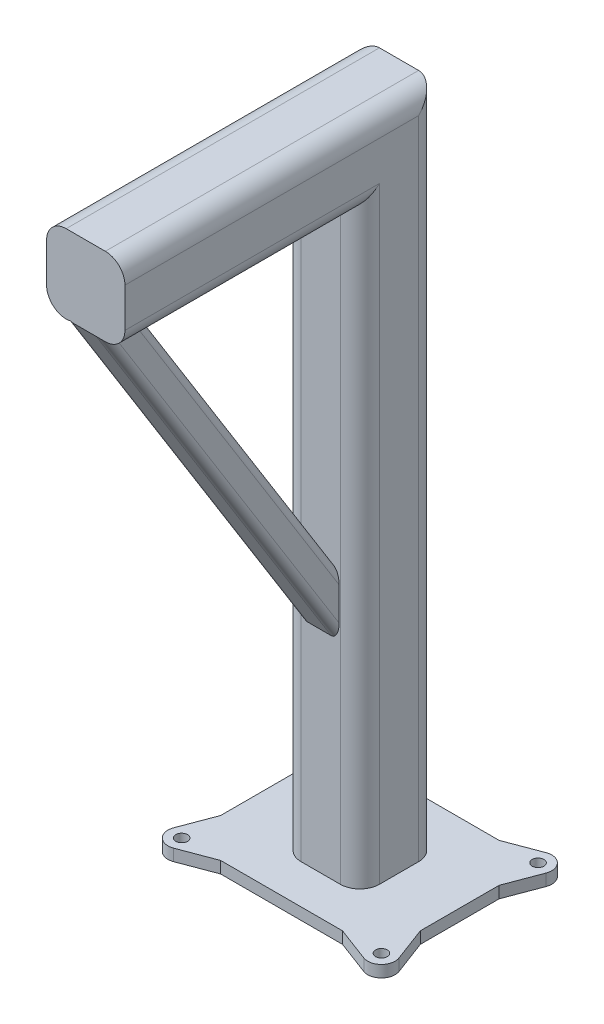
SolidWorks part; units mm, degrees
ref_plane "前视基准面" through (0, 0, 0) normal (0, 0, 1) x (1, 0, 0)
ref_plane "上视基准面" through (0, 0, 0) normal (0, 1, 0) x (1, 0, 0)
ref_plane "右视基准面" through (0, 0, 0) normal (1, 0, 0) x (0, 0, -1)
other "Configuration Table"
sketch "Sketch1" plane through (0, 0, 0) normal (0, 1, 0) x (1, 0, 0)
  line L0 (-24.2665, 23.2754) -> (-15.5689, 20)
  line L10 (24.2665, 23.2754) -> (15.5689, 20)
  line L11 (24.2665, -23.2754) -> (15.5689, -20)
  line L12 (-24.2665, -23.2754) -> (-15.5689, -20)
  line L13 (-28.7754, 18.7665) -> (-25.5, 10.0689)
  line L14 (28.7754, 18.7665) -> (25.5, 10.0689)
  line L15 (28.7754, -18.7665) -> (25.5, -10.0689)
  line L16 (-28.7754, -18.7665) -> (-25.5, -10.0689)
  line L17 (-25.5, 10.0689) -> (-25.5, -10.0689)
  line L18 (-15.5689, 20) -> (15.5689, 20)
  line L20 (25.5, 10.0689) -> (25.5, -10.0689)
  line L24 (-15.5689, -20) -> (15.5689, -20)
  circle A0 centre (-25.5, 20) radius 1.5
  circle A1 centre (25.5, 20) radius 1.5
  circle A2 centre (25.5, -20) radius 1.5
  circle A3 centre (-25.5, -20) radius 1.5
  arc A4 (-24.2665, 23.2754) -> (-28.7754, 18.7665) centre (-25.5, 20) ccw
  arc A5 (28.7754, 18.7665) -> (24.2665, 23.2754) centre (25.5, 20) ccw
  arc A6 (24.2665, -23.2754) -> (28.7754, -18.7665) centre (25.5, -20) ccw
  arc A7 (-28.7754, -18.7665) -> (-24.2665, -23.2754) centre (-25.5, -20) ccw
  point P0 (0, 0)
  dimension "D1" = 40
  dimension "D2" = 51
extrude "Boss-Extrude2" add sketch "Sketch1" along normal blind 3
sketch "Sketch2" plane through (0, 3, 0) normal (0, 1, 0) x (1, 0, 0)
  line L1 (-17.025, 14.275) -> (17.025, 14.275)
  line L2 (-17.025, 14.275) -> (-17.025, -14.275)
  line L3 (-17.025, -14.275) -> (17.025, -14.275)
  line L4 (17.025, 14.275) -> (17.025, -14.275)
  line L5 (0, -14.275) -> (0, 14.275) construction
  line L6 (-17.025, 0) -> (17.025, 0) construction
  line L7 (-18.5, 16) -> (18.5, 16)
  line L8 (-18.5, 16) -> (-18.5, -16)
  line L9 (-18.5, -16) -> (18.5, -16)
  line L10 (18.5, 16) -> (18.5, -16)
  line L11 (0, -16) -> (0, 16) construction
  line L12 (-18.5, 0) -> (18.5, 0) construction
  line L13 (-6, 8) -> (6, 8)
  line L14 (-6, 8) -> (-6, -8)
  line L15 (-6, -8) -> (6, -8)
  line L16 (6, 8) -> (6, -8)
  line L17 (0, -8) -> (0, 8) construction
  line L18 (-6, 0) -> (6, 0) construction
  circle A0 centre (-6, 8) radius 1.1
  circle A1 centre (6, 8) radius 1.1
  circle A2 centre (6, -8) radius 1.1
  circle A3 centre (-6, -8) radius 1.1
  point P0 (0, 0)
  point P4 (0, 0)
  point P11 (0, 0)
  dimension "D1" = 28.55
  dimension "D2" = 34.05
  dimension "D3" = 32
  dimension "D4" = 37
  dimension "D5" = 16
  dimension "D6" = 12
extrude "Boss-Extrude3" [suppressed] add sketch "Sketch2" along normal blind 15 contours L10 L7 L8 L9 L1 L4 L3 L2
sketch "Sketch3" [suppressed] plane through (0, 0, -14.275) normal (0, 0, 1) x (1, 0, 0)
  line L0 (-17.025, 3) -> (17.025, 3) construction
  line L1 (-6, -4) -> (6, -4)
  line L2 (-6, -4) -> (-6, 10)
  line L3 (-6, 10) -> (6, 10)
  line L4 (6, -4) -> (6, 10)
  line L5 (0, 10) -> (0, -4) construction
  line L6 (-6, 3) -> (6, 3) construction
  circle A0 centre (-6, 10) radius 1.1
  circle A1 centre (6, 10) radius 1.1
  point P0 (0, 3)
  dimension "D1" = 14
  dimension "D2" = 12
extrude "Cut-Extrude1" [suppressed] cut sketch "Sketch3" against normal blind 11 and the other way blind 40 contours L3 A0 L2 | L2 A0 L3 | L4 A1 L3 | L3 A1 L4
sketch "Sketch4" plane through (0, 3, 0) normal (0, 1, 0) x (1, 0, 0)
  line L5 (-10, 10) -> (10, 10)
  line L6 (-10, 10) -> (-10, -10)
  line L7 (-10, -10) -> (10, -10)
  line L8 (10, 10) -> (10, -10)
  line L9 (0, -10) -> (0, 10) construction
  line L10 (-10, 0) -> (10, 0) construction
  point P0 (0, 0)
  dimension "D1" = 20
extrude "Boss-Extrude4" add sketch "Sketch4" along normal blind 170
sketch "Sketch5" plane through (0, 0, 10) normal (0, 0, 1) x (1, 0, 0)
  line L1 (-10, 173) -> (10, 173)
  line L2 (-10, 173) -> (-10, 153)
  line L3 (-10, 153) -> (10, 153)
  line L4 (10, 173) -> (10, 153)
  line L5 (10, 173) -> (10, 3) construction
  dimension "D1" = 20
extrude "Boss-Extrude5" add sketch "Sketch5" along normal blind 60
sketch "Sketch7" plane through (0, 153, 0) normal (0, -1, 0) x (1, 0, 0)
  line L0 (-10, 70) -> (10, 70) construction
  line L1 (-5.2978, 70) -> (4.7022, 70)
  line L2 (-5.2978, 70) -> (-5.2978, 60)
  line L3 (-5.2978, 60) -> (4.7022, 60)
  line L4 (4.7022, 70) -> (4.7022, 60)
  dimension "D1" = 10
sketch "Sketch8" plane through (-10, 0, 0) normal (-1, 0, 0) x (0, 0, 1)
  line L0 (10, 153) -> (-10, 120.9454)
  line L1 (-10, 173) -> (-10, 3) construction
extrude "Boss-Extrude6" add sketch "Sketch7" along direction (0, -0.8484, -0.5293) on the side of the normal blind 120
fillet "Fillet1" radius 5 8 edges at (10, 78, 10) (-10, 78, 10) (-10, 153, 40) (10, 173, 30) (-10, 173, 30) (10, 88, -10) (-10, 88, -10) (10, 153, 40)
fillet "Fillet2" radius 2 4 edges at (4.7022, 112.9318, 35) (-5.2978, 112.9291, 34.9983) (4.7022, 104.9182, 40) (-5.2978, 104.911, 39.9956)
